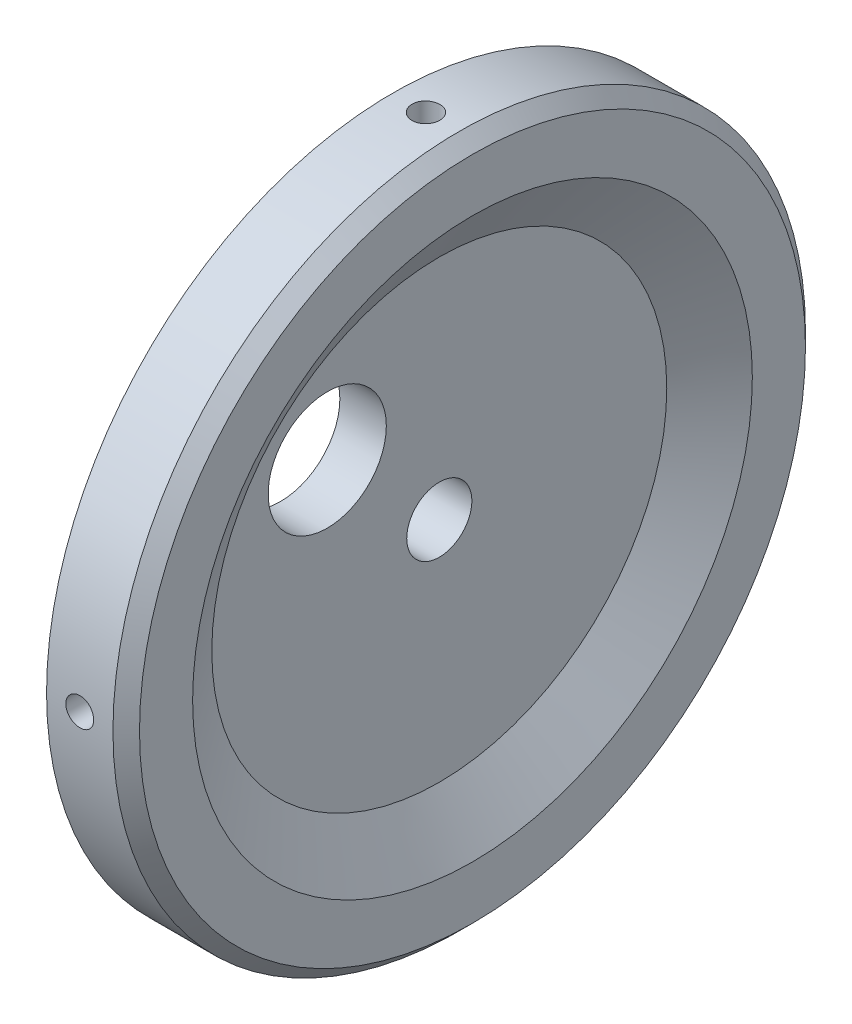
SolidWorks part; units mm, degrees
ref_plane "Front Plane" through (0, 0, 0) normal (0, 0, 1) x (1, 0, 0)
ref_plane "Top Plane" through (0, 0, 0) normal (0, 1, 0) x (1, 0, 0)
ref_plane "Right Plane" through (0, 0, 0) normal (1, 0, 0) x (0, 0, -1)
sketch "Sketch1" plane through (0, 0, 0) normal (0, 1, 0) x (1, 0, 0)
  line L1 (0, -55) -> (0, 55) construction
  line L2 (0, 4.9022) -> (0, 52.15)
  line L3 (0, 52.15) -> (12, 52.15)
  line L4 (12, 52.15) -> (12, 42.15)
  line L8 (7, 4.9022) -> (7, 34.26)
  line L9 (7, 34.26) -> (12, 42.15)
  line L10 (0, 4.9022) -> (7, 4.9022)
  dimension "D2" = 47.2478
  dimension "D3" = 12
  dimension "D4" = 10
  dimension "D6" = 29.3578
sketch "Sketch2" plane through (0, 0, 0) normal (0, 1, 0) x (1, 0, 0)
  line L0 (0, 0) -> (9.8109, 0)
  line L1 (-5.5, 0) -> (5.5, 0) construction
revolve "Revolve1" add sketch "Sketch1" angle 360 about L0
chamfer "Chamfer1" distance 2 angle 45 1 edges at (12, 0, 52.15)
sketch "Sketch3" plane through (7, 0, 0) normal (1, 0, 0) x (0, 0, -1)
  circle A0 centre (-16.8752, 16.2253) radius 8.9
extrude "Cut-Extrude1" cut sketch "Sketch3" against normal blind 10
ref_plane "Plane1" through (0, 0, 52.15) normal (0, 0, 1) x (1, 0, 0)
sketch "Sketch4" plane through (0, 0, 52.15) normal (0, 0, 1) x (1, 0, 0)
  line L0 (12, 0) -> (5, 0)
  line L1 (12, -50.15) -> (12, 50.15) construction
  line L2 (6.6, 0) -> (-6.6, 0) construction
  dimension "D1" = 7
hole_wizard "M5x0.8 Tapped Hole1" positions "Sketch5" profile "Sketch6" tap size "M5x0.8" standard "ANSI Metric"
sketch "Sketch5" plane through (0, 0, 52.15) normal (0, 0, 1) x (1, 0, 0)
  point P0 (5, 0)
sketch "Sketch6" plane through (5, 0, 52.15) normal (1, 0, 0) x (0, -1, 0)
  line L0 (0, 0) -> (0, 10.2618)
  line L1 (0, 10.2618) -> (2.1, 9)
  line L2 (2.1, 9) -> (2.1, 0)
  line L5 (2.1, 0) -> (0, 0)
  line L10 (0, 10.2618) -> (-2.1, 9) construction
  line L11 (0, -6.35) -> (0, 107.95) construction
  dimension "Tap Drill Dia." = 4.2
  dimension "Tap Drill Depth" = 9
  dimension "Drill Angle" = 118
cosmetic thread "Hole Thread1" parameters "D1"=9, "D2"=5
pattern_circular "CirPattern1" count 4 over 360 of "M5x0.8 Tapped Hole1"
cosmetic thread "Hole Thread2" parameters "D1"=9, "D2"=5
cosmetic thread "Hole Thread3" parameters "D1"=9, "D2"=5
cosmetic thread "Hole Thread4" parameters "D1"=9, "D2"=5
cosmetic thread "Hole Thread5" parameters "D1"=9, "D2"=5
cosmetic thread "Hole Thread6" parameters "D1"=9, "D2"=5
